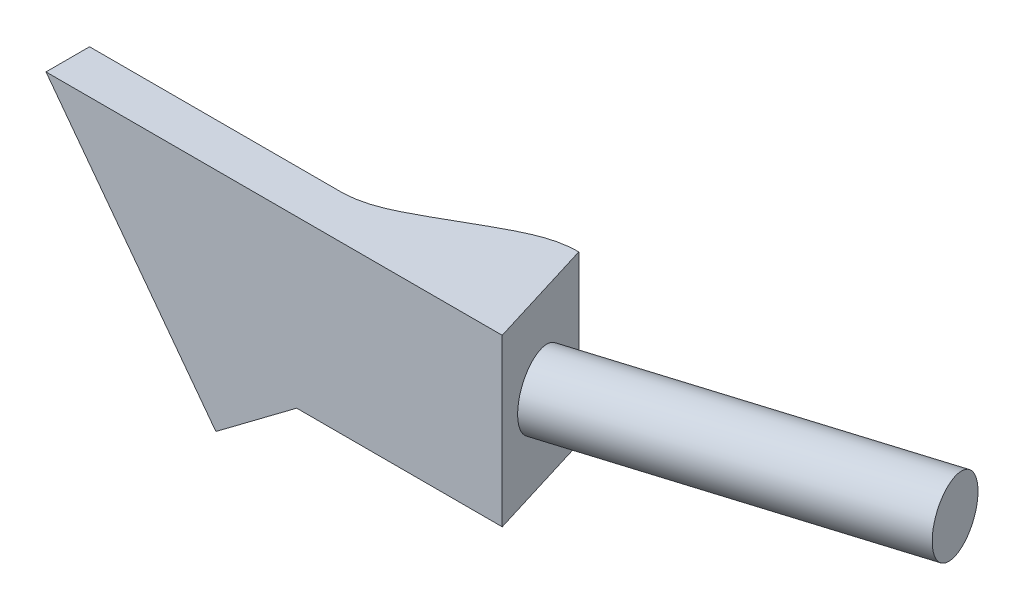
SolidWorks part; units mm, degrees
material "Custom Plastic"
ref_plane "X-Y Datum" through (0, 0, 0) normal (0, 0, 1) x (1, 0, 0)
ref_plane "X-Z Datum" through (0, 0, 0) normal (0, 1, 0) x (1, 0, 0)
ref_plane "Y-Z Datum" through (0, 0, 0) normal (1, 0, 0) x (0, 0, -1)
sketch "Sketch1" plane through (0, 0, 0) normal (0, 0, 1) x (1, 0, 0)
  line L1 (-38.1, -19.05) -> (38.1, -19.05)
  line L2 (-38.1, -19.05) -> (-38.1, 19.05)
  line L3 (-38.1, 19.05) -> (38.1, 19.05)
  line L4 (38.1, -19.05) -> (38.1, 19.05)
  line L5 (-38.1, -19.05) -> (38.1, 19.05) construction
  line L6 (-38.1, 19.05) -> (38.1, -19.05) construction
  point P0 (0, 0)
  dimension "D1" = 38.1
  dimension "D2" = 76.2
extrude "Boss-Extrude1" add sketch "Sketch1" along normal blind 12.7 and the other way blind 12.7
sketch "Sketch2" plane through (0, -19.05, 0) normal (0, -1, 0) x (1, 0, 0)
  line L0 (30.3, -12.7) -> (38.1, 12.7)
  line L1 (-38.1, -12.7) -> (38.1, -12.7) construction
  line L2 (30.3, -12.7) -> (38.1, -12.7)
  line L3 (38.1, -12.7) -> (38.1, 12.7)
  line L4 (34.2, 0) -> (87.6682, -16.4194)
  line L5 (-38.1, 12.7) -> (38.1, 12.7) construction
  line L6 (-9.1056, 2.7) -> (-38.1, 2.7)
  line L7 (-38.1, -12.7) -> (-38.1, 12.7) construction
  line L8 (30.3, -12.7) -> (13.797, -12.7)
  line L9 (-38.1, -12.7) -> (-38.1, 2.7)
  line L10 (30.3, -12.7) -> (-38.1, -12.7)
  spline S0 degree 3 poles (30.3, -12.7) (25.4668, -12.7) (16.7078, -8.7882) (4.4492, -1.2118) (-4.1851, 2.7) (-9.1056, 2.7) knots 0 0 0 0 0.311689 0.688311 1 1 1 1
  point P7 (34.2, 0)
  line M5 (38.1, -12.7) -> (38.1, 12.7)
  line M8 (-38.1, -12.7) -> (38.1, -12.7)
  dimension "D1" = 17.071
  dimension "D2" = 28.9944
  dimension "D3" = 10
  dimension "D4" = 3.81
  dimension "D5" = 3.81
  dimension "D6" = 12.7
  dimension "D7" = 12.7
extrude "Cut-Extrude1" cut sketch "Sketch2" against normal through all contours L4 L0 M8 M5 | L0 L4 L3 | L10 L9 L6 S0 region at (35.0104, -19.05, -7.2716) region at (36.8, -19.05, 3.8341)
sketch "Sketch4" plane through (31.2528, 0, -9.5973) normal (0.9559, 0, -0.2936) x (-0.2936, 0, -0.9559)
  line L1 (-23.325, -19.05) -> (-23.325, 19.05) construction
  circle A0 centre (-10.0397, 0) radius 7.9375
  dimension "D1" = 15.875
  dimension "D2" = 13.2853
extrude "Boss-Extrude2" add sketch "Sketch4" along normal blind 76.2
sketch "Sketch5" plane through (0, 0, 2.7) normal (0, 0, -1) x (-1, 0, 0)
  line L0 (38.1, -19.05) -> (66.6759, 19.05)
  line L1 (66.6759, 19.05) -> (38.1, 19.05)
  line L2 (0, 0) -> (72.4016, 0) construction
  line L3 (72.4016, 0) -> (-7.6416, 60.0343) construction
  line L4 (38.1, 19.05) -> (38.1, -19.05)
  line L5 (9.1056, -19.05) -> (27.6616, -32.9674)
  line L6 (27.6616, -32.9674) -> (38.1, -19.05)
  line L7 (38.1, -19.05) -> (9.1056, -19.05)
  line M4 (9.1056, -19.05) -> (38.1, -19.05)
  line M5 (38.1, -19.05) -> (38.1, 19.05)
  dimension "D1" = 36.871
extrude "Boss-Extrude3" add sketch "Sketch5" against normal up to surface (10 mm away) contours L5 L6 M4 | L0 L1 M5 region at (-47.6253, 6.35, 2.7) region at (-24.9558, -23.6891, 2.7) up to face at (0, 0, 12.7)
sketch "Sketch6" [suppressed] plane through (0, 0, 2.7) normal (0, 0, -1) x (-1, 0, 0)
  line L0 (0, 0) -> (115.4941, 0) construction
  line L1 (115.4941, 0) -> (-57.8809, -130.0354) construction
  line L2 (38.1, 19.05) -> (66.6759, -19.05)
  line L3 (66.6759, -19.05) -> (38.1, -19.05)
  line L4 (38.1, -19.05) -> (38.1, 19.05)
  line L5 (38.1, 19.05) -> (27.6616, 32.9674)
  line L6 (27.6616, 32.9674) -> (9.1056, 19.05)
  line L7 (9.1056, 19.05) -> (38.1, 19.05) construction
  line L8 (9.1056, 19.05) -> (38.1, 19.05)
  line M5 (38.1, -19.05) -> (38.1, 19.05)
  line M6 (38.1, 19.05) -> (9.1056, 19.05)
  dimension "D1" = 36.871
extrude "Boss-Extrude4" [suppressed] add sketch "Sketch6" against normal up to surface (10 mm away) contours L3 L2 M5 | L5 L6 M6 up to face at (-5.4486, -6.5935, 12.7)
